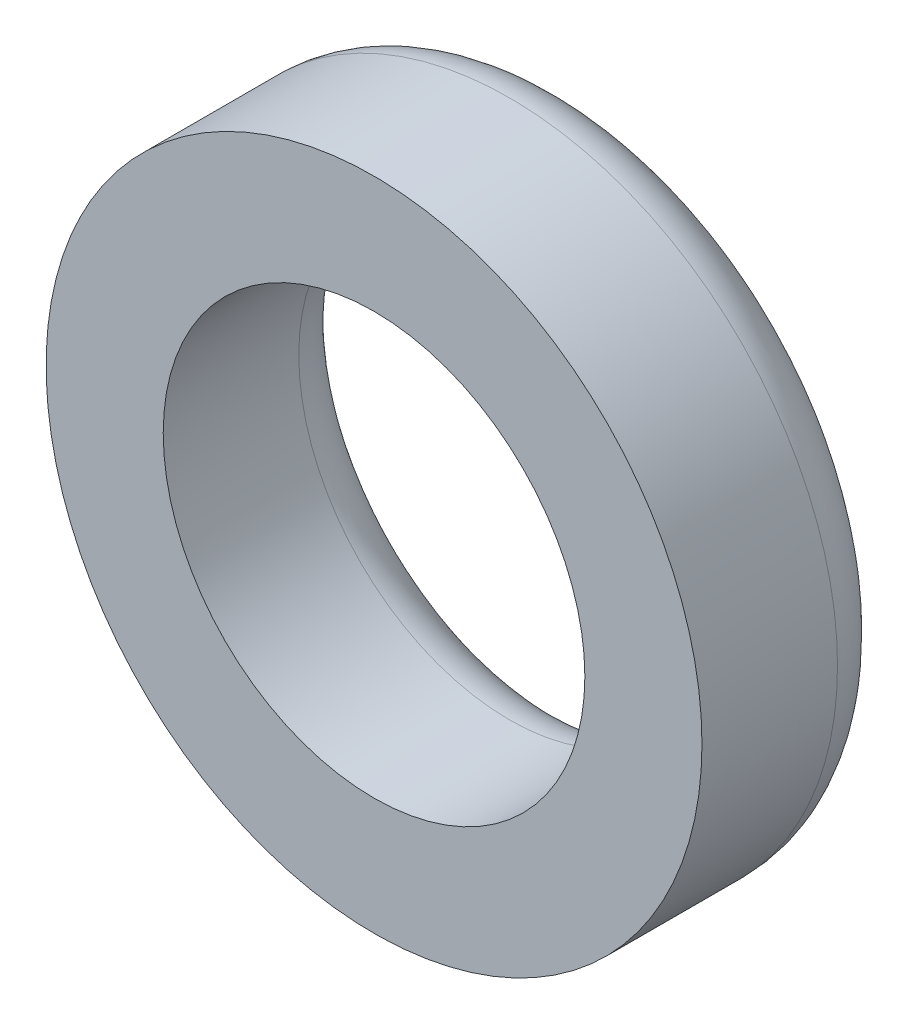
SolidWorks part; units mm, degrees
material "0.6010 (EN-GJL-100)"
ref_plane "Alzado" through (0, 0, 0) normal (0, 0, 1) x (1, 0, 0)
ref_plane "Planta" through (0, 0, 0) normal (0, 1, 0) x (1, 0, 0)
ref_plane "Vista lateral" through (0, 0, 0) normal (1, 0, 0) x (0, 0, -1)
sketch "Croquis1" plane through (0, 0, 0) normal (0, 1, 0) x (1, 0, 0)
  line L0 (0, 0) -> (0, 5.2649) construction
  line L1 (6.3, 0) -> (9.8, 0)
  line L2 (6.3, 0) -> (6.3, 5.8)
  line L3 (6.3, 5.8) -> (9.8, 5.8)
  line L4 (9.8, 0) -> (9.8, 5.8)
  dimension "D1" = 19.6
  dimension "D2" = 12.6
  dimension "D3" = 5.8
revolve "Revolución1" add sketch "Croquis1" angle 360 about L0
fillet "Redondeo1" 2 edges at (6.3, 0, -5.8) (9.8, 0, -5.8) type full round first side face at (6.3, 0, 0) second side face at (9.8, 0, -5.8) middle face at (6.3, 0, -5.8)
